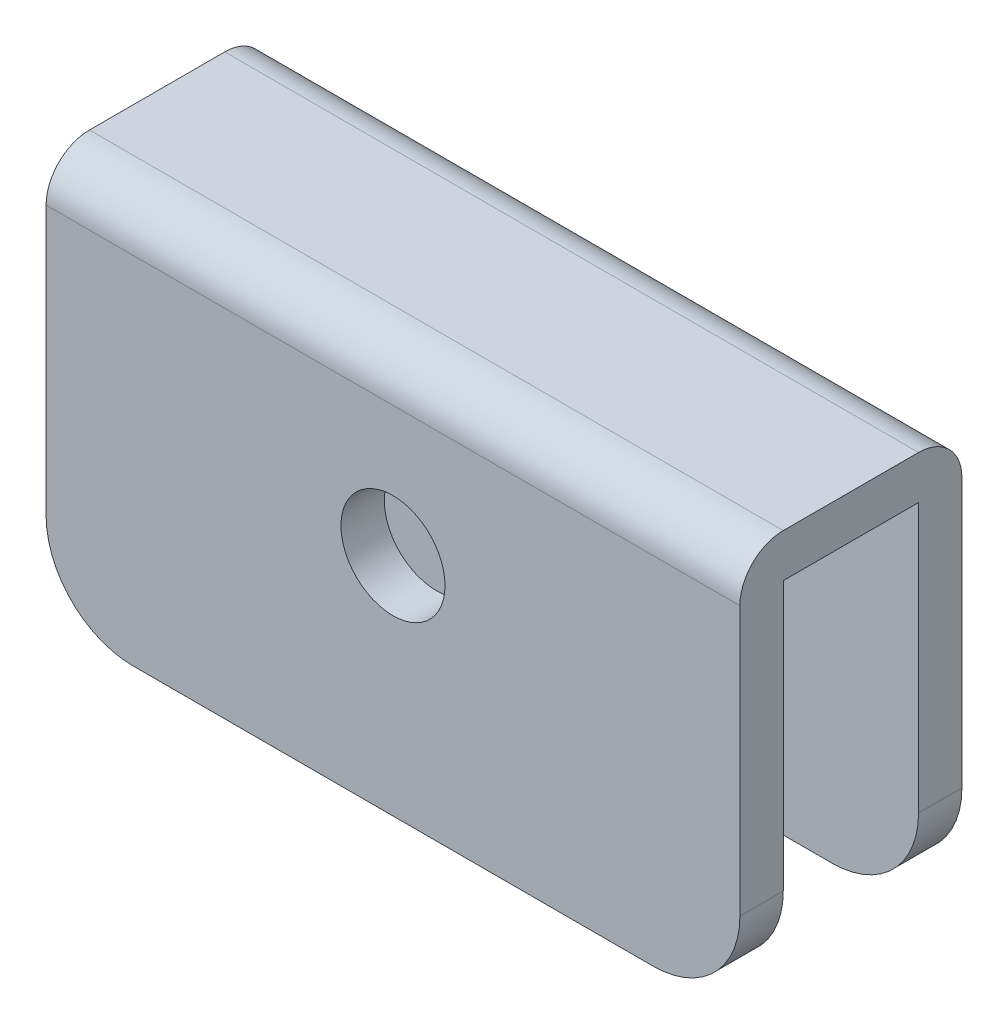
SolidWorks part; units mm, degrees
ref_plane "Front Plane" through (0, 0, 0) normal (0, 0, 1) x (1, 0, 0)
ref_plane "Top Plane" through (0, 0, 0) normal (0, 1, 0) x (1, 0, 0)
ref_plane "Right Plane" through (0, 0, 0) normal (1, 0, 0) x (0, 0, -1)
sketch "Sketch1" plane through (0, 0, 0) normal (0, 0, 1) x (1, 0, 0)
  line L1 (-20, 11.5) -> (20, 11.5)
  line L2 (-20, 11.5) -> (-20, -11.5)
  line L3 (-20, -11.5) -> (20, -11.5)
  line L4 (20, 11.5) -> (20, -11.5)
  line L5 (-20, 11.5) -> (20, -11.5) construction
  line L6 (-20, -11.5) -> (20, 11.5) construction
  point P0 (0, 0)
  dimension "D1" = 40
  dimension "D2" = 23
extrude "Boss-Extrude1" add sketch "Sketch1" along normal blind 6.4 and the other way blind 6.4
sketch "Sketch2" plane through (0, 0, 0) normal (1, 0, 0) x (0, 0, -1)
  line L0 (6.4, -11.5) -> (-6.4, -11.5) construction
  line L1 (-3.9, -11.5) -> (3.9, -11.5)
  line L2 (-3.9, -11.5) -> (-3.9, 9)
  line L3 (-3.9, 9) -> (3.9, 9)
  line L4 (3.9, -11.5) -> (3.9, 9)
  line L5 (-6.4, -11.5) -> (-6.4, 11.5) construction
  line L6 (6.4, -11.5) -> (6.4, 11.5) construction
  line L7 (6.4, 11.5) -> (-6.4, 11.5) construction
  dimension "D1" = 2.5
  dimension "D2" = 2.5
  dimension "D3" = 2.5
extrude "Cut-Extrude1" cut sketch "Sketch2" against normal up to surface and the other way up to surface up to face at (-20, 0, 0) other way up to face at (20, 0, 0)
fillet "Fillet1" radius 5 4 edges at (-20, -11.5, -5.15) (-20, -11.5, 5.15) (20, -11.5, -5.15) (20, -11.5, 5.15)
fillet "Fillet2" radius 2.5 2 edges at (0, 11.5, -6.4) (0, 11.5, 6.4)
sketch "Sketch3" plane through (0, 0, 0) normal (0, 0, 1) x (1, 0, 0)
  line L0 (-20, 11.5) -> (20, 11.5) construction
  circle A0 centre (0, 1.5) radius 3
  point P4 (-2.9531, 3.5)
  dimension "D1" = 6
  dimension "D2" = 10
extrude "Cut-Extrude2" cut sketch "Sketch3" against normal up to surface and the other way up to surface up to face at (0, -3.3452, -6.4) other way up to face at (0, -3.3452, 6.4)
